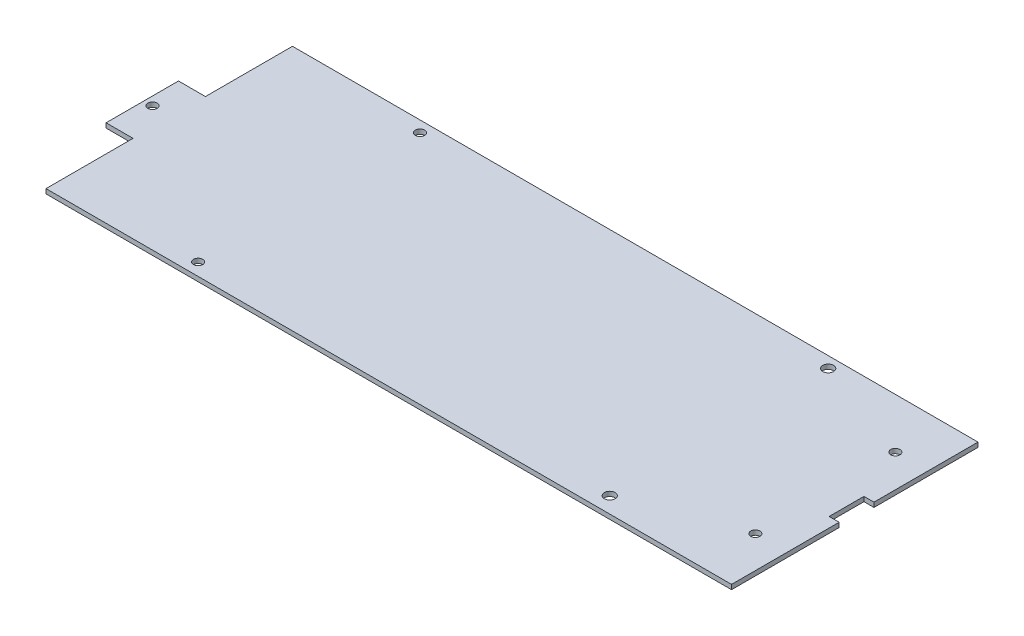
SolidWorks part; units mm, degrees
ref_plane "Front Plane" through (0, 0, 0) normal (0, 0, 1) x (1, 0, 0)
ref_plane "Top Plane" through (0, 0, 0) normal (0, 1, 0) x (1, 0, 0)
ref_plane "Right Plane" through (0, 0, 0) normal (1, 0, 0) x (0, 0, -1)
sketch "Sketch1" plane through (0, 0, 0) normal (0, 1, 0) x (1, 0, 0)
  line L0 (-302.2355, 23.5) -> (-284.7355, 23.5)
  line L1 (-284.7355, 80) -> (160.2645, 80)
  line L2 (-284.7355, 80) -> (-284.7355, 23.5)
  line L5 (-296.7465, -73.7679) -> (-296.7465, 76.0921) construction
  line L6 (-284.7355, 80) -> (-286.6881, 66.0337) construction
  line L7 (-302.2355, 23.5) -> (-302.2355, -23.5)
  line L8 (-302.2355, -23.5) -> (-284.7355, -23.5)
  line L9 (-284.7355, -23.5) -> (-284.7355, -80)
  line L10 (-284.7355, 31.0446) -> (-284.7355, 23.5) construction
  line L11 (160.2645, 80) -> (160.2645, 12.4621)
  line L12 (160.2645, 12.4621) -> (153.7645, 12.4621)
  line L13 (-302.2355, 0) -> (-26.2365, 1.1621) construction
  line L14 (161.6735, 9.4621) -> (169.6735, 9.4621) construction
  line L15 (153.7645, 12.4621) -> (153.7645, -10.1379)
  line L16 (153.7645, -10.1379) -> (160.2645, -10.1379)
  line L17 (169.6735, -7.1379) -> (161.6735, -7.1379) construction
  line L18 (160.2645, -10.1379) -> (160.2645, -80)
  line L19 (160.2645, -80) -> (-284.7355, -80)
  line L20 (-194.7355, 72.7736) -> (70.2645, 72.7736) construction
  circle A0 centre (-296.7465, 1.1621) radius 3
  circle A1 centre (-194.7355, 72.7736) radius 3
  circle A2 centre (70.2645, 72.7736) radius 3.5
  circle A3 centre (70.8641, -69.6343) radius 3.5
  circle A4 centre (-194.1265, -71.8658) radius 3
  circle A5 centre (139.1024, 47.5) radius 3
  circle A6 centre (139.4867, -43.7819) radius 3
  point P4 (0, 0)
  dimension "D9" = 6.5
  dimension "D12" = 6
  dimension "D3" = 6
  dimension "D15" = 6
  dimension "D16" = 7
  dimension "D1" = 56.5
  dimension "D2" = 56.5
  dimension "D4" = 3
  dimension "D5" = 3
  dimension "D6" = 17.5
  dimension "D7" = 445
  dimension "D8" = 69.8621
  dimension "D10" = 160
  dimension "D11" = 67.5379
  dimension "D13" = 90
  dimension "D14" = 90
  dimension "D17" = 32.5
extrude "Boss-Extrude1" add sketch "Sketch1" along normal blind 3 from offset 2 contours L8 L9 L1 L2 L0 L7 region at (-65.4442, 0, 0.0064)
